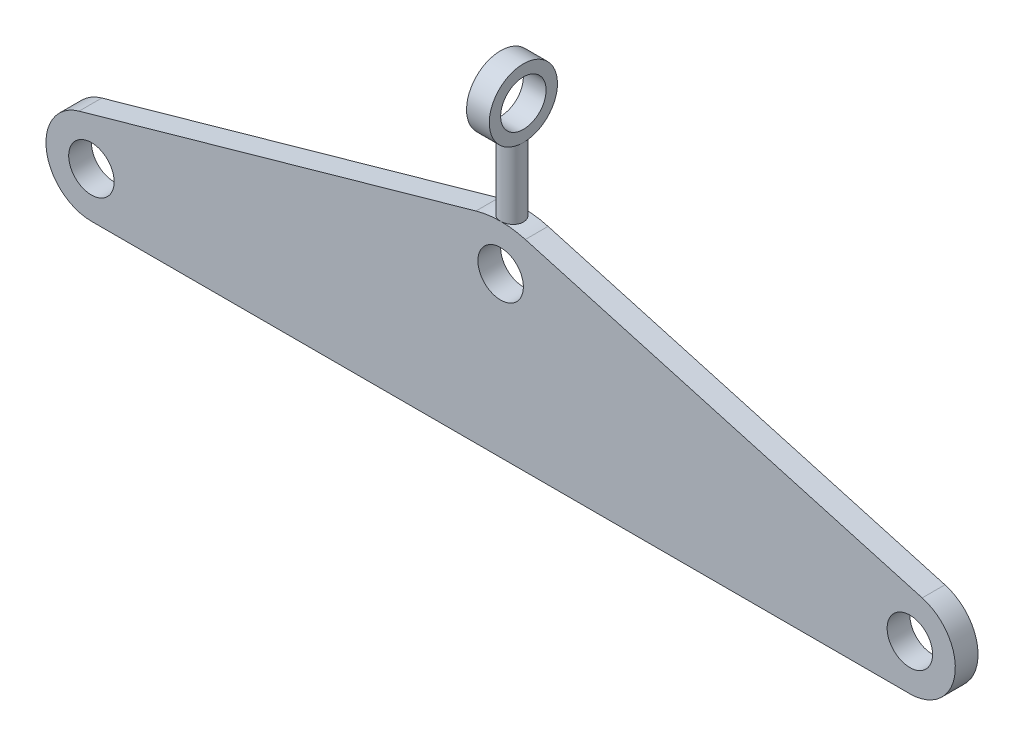
SolidWorks part; units mm, degrees
ref_plane "前视基准面" through (0, 0, 0) normal (0, 0, 1) x (1, 0, 0)
ref_plane "上视基准面" through (0, 0, 0) normal (0, 1, 0) x (1, 0, 0)
ref_plane "右视基准面" through (0, 0, 0) normal (1, 0, 0) x (0, 0, -1)
other "Configuration Table"
sketch "草图1" plane through (0, 0, 0) normal (0, 0, 1) x (1, 0, 0)
  line L0 (-10.8607, 88.4973) -> (-185.4303, 39.2487)
  line L1 (-180, 0) -> (180, 0)
  line L2 (185.4303, 39.2487) -> (10.8607, 88.4973)
  line L3 (0, 91.5613) -> (0, 0) construction
  arc A0 (180, 0) -> (185.4303, 39.2487) centre (180, 20) ccw
  arc A1 (-180, 0) -> (-185.4303, 39.2487) centre (-180, 20) cw
  arc A2 (10.8607, 88.4973) -> (-10.8607, 88.4973) centre (0, 50) ccw
  circle A3 centre (-180, 20) radius 10
  circle A4 centre (180, 20) radius 10
  circle A5 centre (0, 70) radius 10
  dimension "D1" = 20
  dimension "D2" = 40
  dimension "D3" = 400
  dimension "D4" = 90
  dimension "D5" = 20
  dimension "D6" = 20
  dimension "D7" = 20
  dimension "D8" = 70
extrude "凸台-拉伸1" add sketch "草图1" along normal blind 10
sketch "草图2" plane through (0, 0, 0) normal (0, -1, 0) x (1, 0, 0)
  line L0 (0, 0) -> (0, 10) construction
  line L1 (-180, 0) -> (180, 0) construction
  line L2 (-180, 10) -> (180, 10) construction
  circle A0 centre (0, 5) radius 5
  dimension "D1" = 10
extrude "凸台-拉伸2" add sketch "草图2" against normal blind 40 from offset 85 offset against normal yes
sketch "草图3" plane through (0, 0, 0) normal (1, 0, 0) x (0, 0, -1)
  line L0 (0, 125) -> (-10, 125) construction
  line L1 (-5, 135) -> (-5, 125) construction
  line L2 (0, 125) -> (-10, 125) construction
  circle A0 centre (-5, 135) radius 10
  circle A1 centre (-5, 135) radius 15
  point P8 (-5, 125)
  dimension "D1" = 20
  dimension "D2" = 30
extrude "凸台-拉伸3" add sketch "草图3" along normal blind 5 and the other way blind 5
